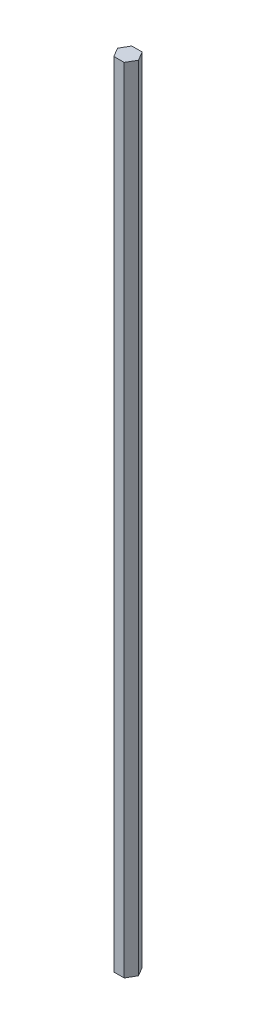
SolidWorks part; units mm, degrees
material "6061-T6 (SS)"
ref_plane "Front" through (0, 0, 0) normal (0, 0, 1) x (1, 0, 0)
ref_plane "Top" through (0, 0, 0) normal (0, 1, 0) x (1, 0, 0)
ref_plane "Right" through (0, 0, 0) normal (1, 0, 0) x (0, 0, -1)
sketch "Sketch1" plane through (0, 0, 0) normal (0, 1, 0) x (1, 0, 0)
  line L1 (7.3323, 0) -> (3.6662, 6.35)
  line L2 (3.6662, 6.35) -> (-3.6662, 6.35)
  line L3 (-3.6662, 6.35) -> (-7.3323, 0)
  line L4 (-7.3323, 0) -> (-3.6662, -6.35)
  line L5 (-3.6662, -6.35) -> (3.6662, -6.35)
  line L6 (3.6662, -6.35) -> (7.3323, 0)
  circle A0 centre (0, 0) radius 6.35 construction
  dimension "D1" = 12.7
extrude "Boss-Extrude1" add sketch "Sketch1" along normal blind 558.8
ref_axis "Axis1" through (0, 50, 0) along (0, -1, 0)
